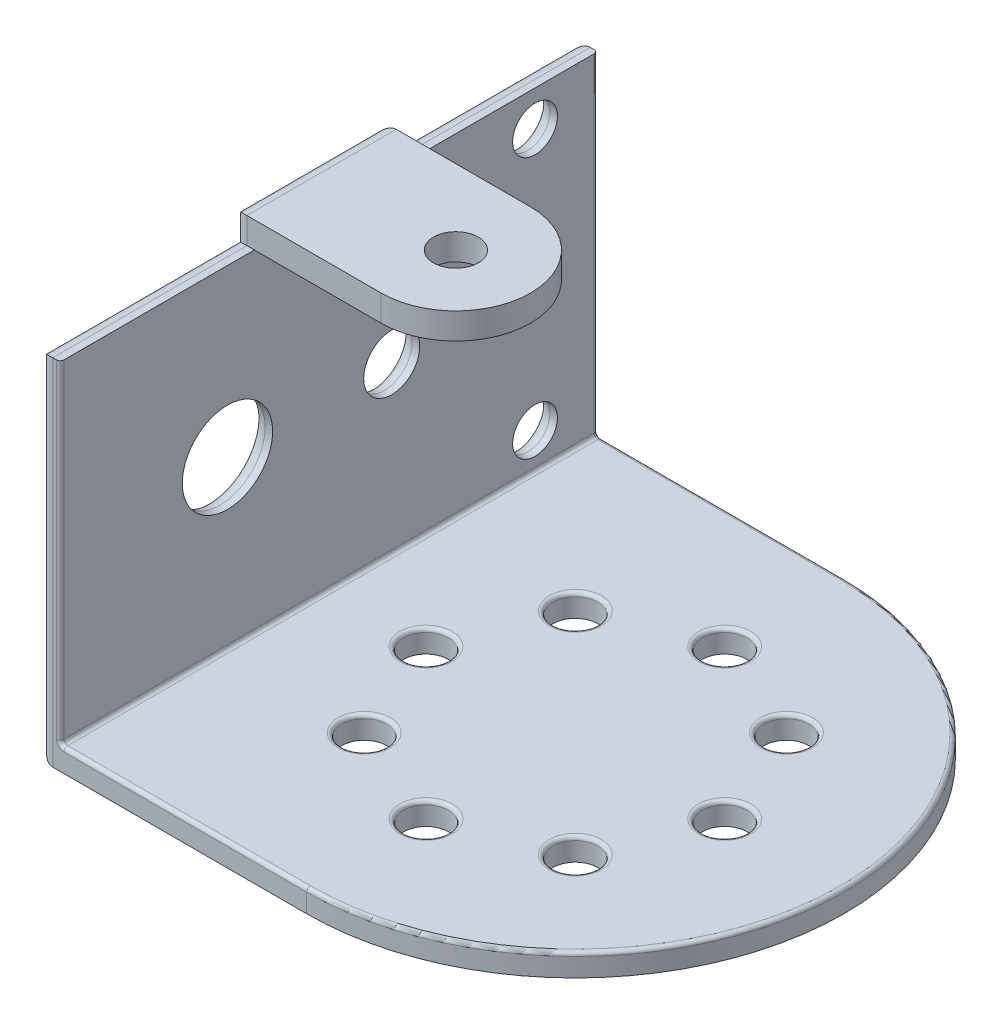
SolidWorks part; units mm, degrees
material "PLA"
ref_plane "Alzado" through (0, 0, 0) normal (0, 0, 1) x (1, 0, 0)
ref_plane "Planta" through (0, 0, 0) normal (0, 1, 0) x (1, 0, 0)
ref_plane "Vista lateral" through (0, 0, 0) normal (1, 0, 0) x (0, 0, -1)
sketch "Croquis1" plane through (0, 0, 0) normal (1, 0, 0) x (0, 0, -1)
  line L0 (18, 0) -> (-18, 0) construction
  line L1 (-18, -11.125) -> (18, -11.125)
  line L2 (-18, -11.125) -> (-18, 11.125)
  line L3 (-18, 11.125) -> (18, 11.125)
  line L4 (18, -11.125) -> (18, 11.125)
  line L5 (-18, -11.125) -> (18, 11.125) construction
  line L6 (-18, 11.125) -> (18, -11.125) construction
  circle A0 centre (13.8, 8.745) radius 1.5
  circle A1 centre (-6.8, 0) radius 3.025
  circle A2 centre (13.8, -8.745) radius 1.5
  circle A3 centre (4.2, 0) radius 1.875
  point P0 (0, 0)
  dimension "D3" = 4.2
  dimension "D5" = 3
  dimension "D6" = 6.05
  dimension "D8" = 13.8
  dimension "D9" = 3.75
  dimension "D1" = 22.25
  dimension "D2" = 36
  dimension "D4" = 2.38
  dimension "D7" = 11.2
extrude "Saliente-Extruir1" add sketch "Croquis1" along normal blind 1.5
sketch "Croquis3" plane through (0, -11.125, 0) normal (0, -1, 0) x (1, 0, 0)
  line L0 (0, 18) -> (0, -18) construction
  line L1 (18, -18) -> (0, -18)
  line L2 (18, 18) -> (0, 18)
  line L3 (0, 18) -> (0, -18)
  arc A0 (18, -18) -> (18, 18) centre (18, 0) ccw
  dimension "D1" = 36
  dimension "D2" = 18
extrude "Extruir-Lámina1" [suppressed] add sketch "Croquis3" along normal blind 1.5 separate body thin thin type one direction wall 10
extrude "Saliente-Extruir3" add sketch "Croquis3<2>" along normal blind 1.5
sketch "Croquis3<2>" plane through (0, -11.125, 0) normal (0, -1, 0) x (1, 0, 0) same geometry as "Croquis3"
sketch "Croquis4" plane through (0, 11.125, 0) normal (0, 1, 0) x (1, 0, 0)
  line L0 (10, 5) -> (0, 5)
  line L1 (0, 18) -> (0, -18) construction
  line L2 (10, -5) -> (0, -5)
  line L7 (0, 18) -> (0, -18)
  line L8 (0, -18) -> (1.5, -18)
  line L9 (1.5, -18) -> (1.5, 18)
  line L10 (1.5, 18) -> (0, 18)
  line L11 (0, 5) -> (0, -5)
  arc A0 (10, -5) -> (10, 5) centre (10, 0) ccw
  dimension "D1" = 10
  dimension "D2" = 10
  dimension "D3" = 0
extrude "Saliente-Extruir4" add sketch "Croquis4" along normal blind 1.75
sketch "Croquis5" plane through (0, 12.875, 0) normal (0, 1, 0) x (1, 0, 0)
  circle A0 centre (10, 0) radius 1.5
  dimension "D1" = 3
extrude "Cortar-Extruir1" cut sketch "Croquis5" against normal up to next
sketch "Croquis7" plane through (0, -12.625, 0) normal (0, -1, 0) x (1, 0, 0)
  line L0 (18, 0) -> (36, 0) construction
  arc A0 (18, -18) -> (18, 18) centre (18, 0) ccw construction
  circle A1 centre (28, 0) radius 1.5
  circle A2 centre (25.0711, -7.0711) radius 1.5
  circle A3 centre (18, -10) radius 1.5
  circle A4 centre (10.9289, -7.0711) radius 1.5
  circle A5 centre (8, 0) radius 1.5
  circle A6 centre (10.9289, 7.0711) radius 1.5
  circle A7 centre (18, 10) radius 1.5
  circle A8 centre (25.0711, 7.0711) radius 1.5
  point P25 (18, 0)
  dimension "D1" = 3
  dimension "D2" = 10
  dimension "D4" = 28
  dimension "D3" = 8
extrude "Cortar-Extruir2" cut sketch "Croquis7" against normal up to next
fillet "Redondeo1" [suppressed] radius 1
fillet "Redondeo2" radius 1 12 edges at (0, 0, -6.075) (0, 0, 3.775) (0, 11.125, -11.5) (0, 12, -5) (0, 12.875, 0) (0, 12, 5) (0, 11.125, 11.5) (0, -0.75, 18) (0, -12.625, 0) (0, -0.75, -18) (0, 8.745, -15.3) (0, -8.745, -12.3)
fillet "Redondeo3" radius 0.25 14 edges at (1.5, 0, -18) (1.5, 0, 18) (9.75, -11.125, -18) (36, -11.125, 0) (9.75, -11.125, 18) (1.5, -11.125, 0) (28, -11.125, -1.5) (25.0711, -11.125, -8.5711) (18, -11.125, -11.5) (10.9289, -11.125, -8.5711) (8, -11.125, -1.5) (10.9289, -11.125, 5.5711) (18, -11.125, 8.5) (25.0711, -11.125, 5.5711)
